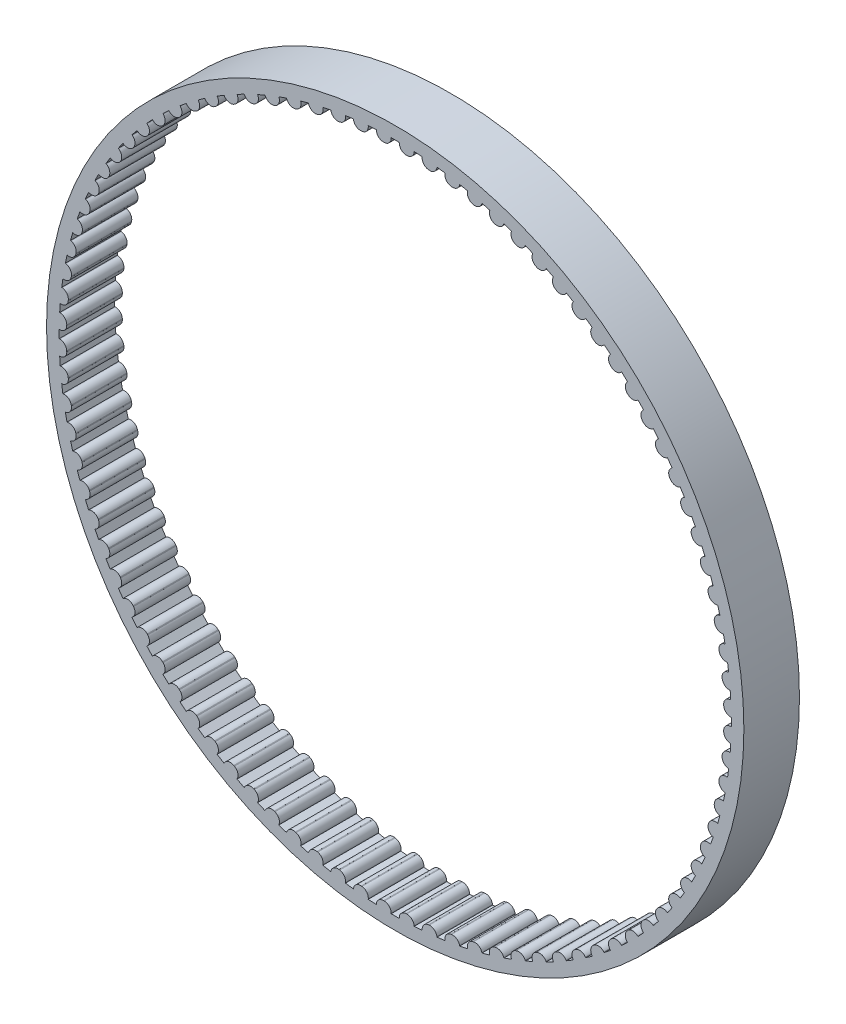
SolidWorks part; units mm, degrees
ref_plane "Front Plane" through (0, 0, 0) normal (0, 0, 1) x (1, 0, 0)
ref_plane "Top Plane" through (0, 0, 0) normal (0, 1, 0) x (1, 0, 0)
ref_plane "Right Plane" through (0, 0, 0) normal (1, 0, 0) x (0, 0, -1)
sketch "Sketch1" plane through (0, 0, 0) normal (0, 0, 1) x (1, 0, 0)
  line L0 (0, 35) -> (0, 37.5) construction
  circle A0 centre (0, 0) radius 32.5
  circle A1 centre (0, 0) radius 34.5
  dimension "D1" = 65
  dimension "D2" = 2
extrude "Boss-Extrude3" add sketch "Sketch1" along normal blind 5.5
sketch "Sketch4" plane through (0, 0, 5.5) normal (0, 0, 1) x (1, 0, 0)
  line L0 (0, 40.7249) -> (0, 15.5386) construction
  line L1 (-0.4, 33.1998) -> (-0.4, 33.25)
  line L2 (-0.4, 33.25) -> (0.4, 33.25)
  line L3 (0.4, 33.25) -> (0.4, 33.1998)
  line L4 (-3.0113, 32.5) -> (1.7241, 32.5) construction
  line L5 (-1.1023, 32.4998) -> (-1.15, 32.5)
  line L6 (-1.15, 32.5) -> (-1.15, 32)
  line L7 (-1.15, 32) -> (1.15, 32)
  line L8 (1.15, 32) -> (1.15, 32.5)
  line L9 (1.15, 32.5) -> (1.1023, 32.4998)
  circle A0 centre (0, 0) radius 32.5 construction
  circle A1 centre (0, 0) radius 32.5 construction
  arc A2 (1.1023, 32.4998) -> (0.4, 33.1998) centre (1.1, 33.1998) cw
  arc A3 (-1.1023, 32.4998) -> (-0.4, 33.1998) centre (-1.1, 33.1998) ccw
  point P9 (0, 33.25)
  point P20 (0.4, 32.4975)
  point P23 (-0.4, 32.4975)
  dimension "D4" = 0.7
  dimension "D1" = 0.8
  dimension "D2" = 0.75
  dimension "D3" = 0.75
  dimension "D5" = 0.5
extrude "Cut-Extrude1" cut sketch "Sketch4" against normal through all
ref_axis "Axis1" through (0, 0, 5.5) along (0, 0, -1)
pattern_circular "CirPattern1" count 92 over 360 about axis through (0, 0, 5.5) along (0, 0, -1) of "Cut-Extrude1"
